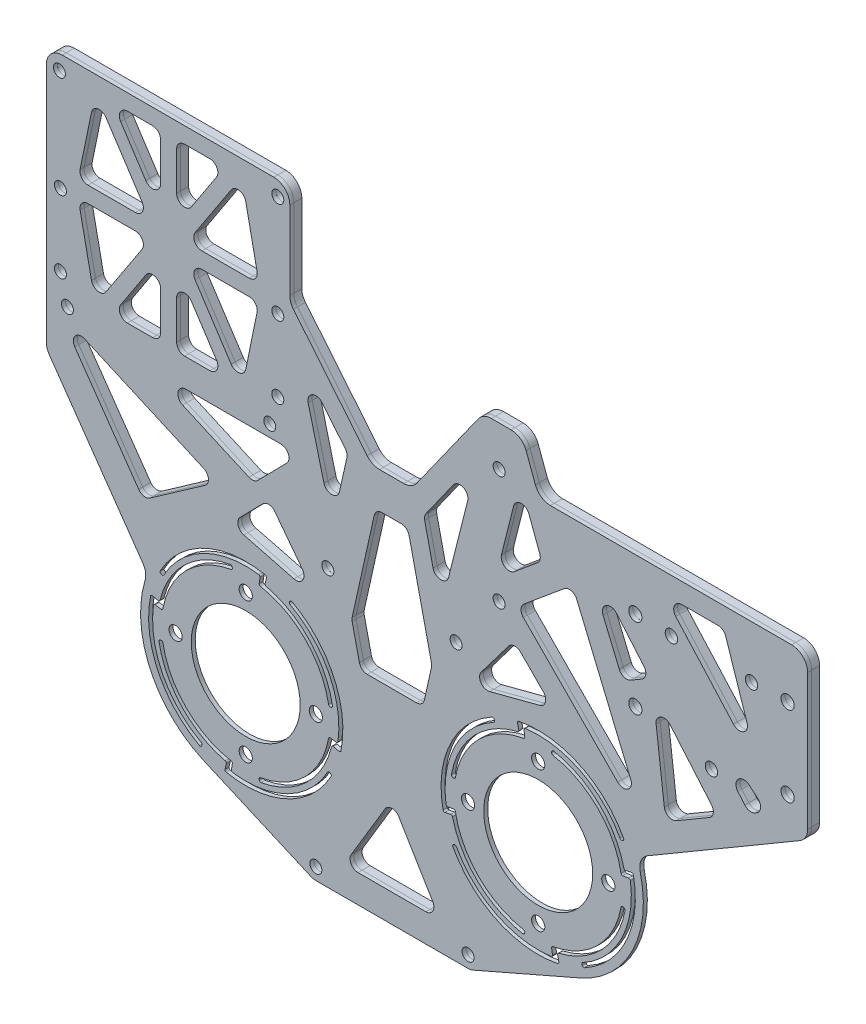
SolidWorks part; units mm, degrees
material "碳1"
ref_plane "前视基准面" through (0, 0, 0) normal (0, 0, 1) x (1, 0, 0)
ref_plane "上视基准面" through (0, 0, 0) normal (0, 1, 0) x (1, 0, 0)
ref_plane "右视基准面" through (0, 0, 0) normal (1, 0, 0) x (0, 0, -1)
sketch "草图1" plane through (0, 0, 0) normal (0, 0, 1) x (1, 0, 0)
  line L0 (-404.6498, 0) -> (19827.8382, 0) construction
  line L1 (0, -404.6498) -> (0, 19827.8382) construction
  circle A0 centre (36.5, 0) radius 17.5 construction
  circle A1 centre (-36.5, 0) radius 17.5 construction
  circle A2 centre (19, 0) radius 1.65
  circle A3 centre (36.5, 17.5) radius 1.65
  circle A4 centre (54, 0) radius 1.65
  circle A5 centre (36.5, -17.5) radius 1.65
  circle A6 centre (-19, 0) radius 1.65
  circle A7 centre (-36.5, -17.5) radius 1.65
  circle A8 centre (-54, 0) radius 1.65
  circle A9 centre (-36.5, 17.5) radius 1.65
  circle A10 centre (36.5, 0) radius 13.6
  circle A11 centre (-36.5, 0) radius 13.6
  circle A12 centre (36.5, 0) radius 21
  circle A13 centre (-36.5, 0) radius 21
  point P20 (36.5, 0)
  dimension "D1" = 73
  dimension "D2" = 35
  dimension "D3" = 3.3
  dimension "D5" = 27.2
  dimension "D6" = 42
  dimension "D4" = 4
extrude "凸台-拉伸1" add sketch "草图1" along normal blind 3
sketch "草图2" plane through (0, 0, 3) normal (0, 0, 1) x (1, 0, 0)
  line L0 (0, -1000) -> (0, 49000) construction
  line L1 (36.5, -1000) -> (36.5, 49000) construction
  line L2 (-965, 0) -> (49035, 0) construction
  line L3 (36.1795, 0.8807) -> (-17028.2448, 46885.001) construction
  line L4 (14.7709, 3.4416) -> (15.7585, 3.2851)
  line L5 (13.5362, -3.6371) -> (15.7585, -3.2851)
  line L6 (57.9785, 4.7617) -> (60.1752, 5.2487)
  line L7 (31.7383, 21.4785) -> (31.2513, 23.6752)
  line L8 (25.3026, 21.51) -> (25.7643, 20.623)
  line L9 (58.01, 11.1974) -> (57.123, 10.7357)
  line L10 (39.9416, 21.7291) -> (39.7851, 20.7415)
  line L11 (32.8629, 22.9638) -> (33.2149, 20.7415)
  line L12 (41.2617, -21.4785) -> (41.7487, -23.6752)
  line L13 (47.6974, -21.51) -> (47.2357, -20.623)
  line L14 (58.2291, -3.4416) -> (57.2415, -3.2851)
  line L15 (59.4638, 3.6371) -> (57.2415, 3.2851)
  line L16 (15.0215, -4.7617) -> (12.8248, -5.2487)
  line L17 (14.99, -11.1974) -> (15.877, -10.7357)
  line L18 (33.0584, -21.7291) -> (33.2149, -20.7415)
  line L19 (40.1371, -22.9638) -> (39.7851, -20.7415)
  line L20 (-40.1371, -22.9638) -> (-39.7851, -20.7415)
  line L21 (-33.0584, -21.7291) -> (-33.2149, -20.7415)
  line L22 (-14.99, -11.1974) -> (-15.877, -10.7357)
  line L23 (-15.0215, -4.7617) -> (-12.8248, -5.2487)
  line L24 (-59.4638, 3.6371) -> (-57.2415, 3.2851)
  line L25 (-58.2291, -3.4416) -> (-57.2415, -3.2851)
  line L26 (-47.6974, -21.51) -> (-47.2357, -20.623)
  line L27 (-41.2617, -21.4785) -> (-41.7487, -23.6752)
  line L28 (-32.8629, 22.9638) -> (-33.2149, 20.7415)
  line L29 (-39.9416, 21.7291) -> (-39.7851, 20.7415)
  line L30 (-58.01, 11.1974) -> (-57.123, 10.7357)
  line L31 (-25.3026, 21.51) -> (-25.7643, 20.623)
  line L32 (-31.7383, 21.4785) -> (-31.2513, 23.6752)
  line L33 (-57.9785, 4.7617) -> (-60.1752, 5.2487)
  line L34 (-13.5362, -3.6371) -> (-15.7585, -3.2851)
  line L35 (-14.7709, 3.4416) -> (-15.7585, 3.2851)
  arc A1 (32.8629, 22.9638) -> (57.123, 10.7357) centre (36.5, 0) cw
  arc A2 (39.9416, 21.7291) -> (57.9785, 4.7617) centre (36.5, 0) cw
  circle A3 centre (36.5, 0) radius 21 construction
  arc A4 (13.5362, -3.6371) -> (25.7643, 20.623) centre (36.5, 0) cw
  arc A5 (14.7709, 3.4416) -> (31.7383, 21.4785) centre (36.5, 0) cw
  arc A6 (25.3026, 21.51) -> (31.2513, 23.6752) centre (36.5, 0) cw
  circle A7 centre (36.5, 0) radius 24.25
  circle A8 centre (36.5, 0) radius 26.25
  arc A9 (59.4638, 3.6371) -> (47.2357, -20.623) centre (36.5, 0) cw
  arc A10 (58.2291, -3.4416) -> (41.2617, -21.4785) centre (36.5, 0) cw
  arc A11 (40.1371, -22.9638) -> (15.877, -10.7357) centre (36.5, 0) cw
  arc A12 (33.0584, -21.7291) -> (15.0215, -4.7617) centre (36.5, 0) cw
  arc A13 (-33.0584, -21.7291) -> (-15.0215, -4.7617) centre (-36.5, 0) ccw
  arc A14 (-40.1371, -22.9638) -> (-15.877, -10.7357) centre (-36.5, 0) ccw
  arc A15 (-58.2291, -3.4416) -> (-41.2617, -21.4785) centre (-36.5, 0) ccw
  arc A16 (-59.4638, 3.6371) -> (-47.2357, -20.623) centre (-36.5, 0) ccw
  circle A17 centre (-36.5, 0) radius 26.25
  circle A18 centre (-36.5, 0) radius 24.25
  arc A19 (-25.3026, 21.51) -> (-31.2513, 23.6752) centre (-36.5, 0) ccw
  arc A20 (-14.7709, 3.4416) -> (-31.7383, 21.4785) centre (-36.5, 0) ccw
  arc A21 (-13.5362, -3.6371) -> (-25.7643, 20.623) centre (-36.5, 0) ccw
  arc A22 (-39.9416, 21.7291) -> (-57.9785, 4.7617) centre (-36.5, 0) ccw
  arc A23 (-32.8629, 22.9638) -> (-57.123, 10.7357) centre (-36.5, 0) ccw
  circle A24 centre (-36.5, 0) radius 21 construction
  circle A25 centre (-36.5, 0) radius 21
  point P50 (36.5, 0)
  point P84 (-36.5, 0)
  circle M14 centre (36.5, 0) radius 21
  dimension "D1" = 18
  dimension "D2" = 20
  dimension "D3" = 1
  dimension "D4" = 4
  dimension "D5" = 1.25
  dimension "D7" = 1
  dimension "D8" = 2
  dimension "D6" = 15
extrude "凸台-拉伸2" add sketch "草图2" against normal blind 3 contours A8 A7 A6 | A6 L8 A4 L5 L4 A5 L7 M14 | L6 A7 L9 A1 L11 L10 A2 M14 | L14 A10 L12 A7 L13 A9 L15 M14 | L18 A12 L16 A7 L17 A11 L19 M14 | A25 L28 A23 L30 A18 L33 A22 L29 | A25 L34 A21 L31 A18 L32 A20 L35 | A17 A18 | A25 L20 A14 L22 A18 L23 A13 L21 | A25 L24 A16 L26 A18 L27 A15 L25 region at (15.2131, 3.0376, 3) region at (33.3646, 21.9042, 3) region at (36.5, -21.3298, 3) region at (58.4042, 3.1354, 3) region at (-39.6354, -21.9042, 3) region at (-57.7869, -3.0376, 3) region at (-15.2359, -1.6735, 3) region at (-39.5376, 21.2869, 3) region at (10.9925, 0, 3) region at (-62.0075, 0, 3)
fillet "圆角1" radius 0.4 32 edges at (39.7851, 20.7415, 1.5) (39.9416, 21.7291, 1.5) (33.2149, 20.7415, 1.5) (32.8629, 22.9638, 1.5) (25.7643, 20.623, 1.5) (47.6974, -21.51, 1.5) (25.3026, 21.51, 1.5) (31.7383, 21.4785, 1.5) (31.2513, 23.6752, 1.5) (41.7487, -23.6752, 1.5) (57.9785, 4.7617, 1.5) (60.1752, 5.2487, 1.5) (12.8248, -5.2487, 1.5) (47.2357, -20.623, 1.5) (59.4638, 3.6371, 1.5) (57.2415, 3.2851, 1.5) (57.2415, -3.2851, 1.5) (58.2291, -3.4416, 1.5) (41.2617, -21.4785, 1.5) (58.01, 11.1974, 1.5) (14.99, -11.1974, 1.5) (15.877, -10.7357, 1.5) (40.1371, -22.9638, 1.5) (39.7851, -20.7415, 1.5) (33.2149, -20.7415, 1.5) (33.0584, -21.7291, 1.5) (15.0215, -4.7617, 1.5) (13.5362, -3.6371, 1.5) (15.7585, -3.2851, 1.5) (14.7709, 3.4416, 1.5) (57.123, 10.7357, 1.5) (15.7585, 3.2851, 1.5)
fillet "圆角2" radius 0.4 32 edges at (-32.8629, 22.9638, 1.5) (-57.123, 10.7357, 1.5) (-14.99, -11.1974, 1.5) (-58.01, 11.1974, 1.5) (-31.7383, 21.4785, 1.5) (-14.7709, 3.4416, 1.5) (-15.7585, 3.2851, 1.5) (-33.2149, 20.7415, 1.5) (-15.7585, -3.2851, 1.5) (-13.5362, -3.6371, 1.5) (-25.7643, 20.623, 1.5) (-47.6974, -21.51, 1.5) (-25.3026, 21.51, 1.5) (-60.1752, 5.2487, 1.5) (-12.8248, -5.2487, 1.5) (-15.0215, -4.7617, 1.5) (-33.0584, -21.7291, 1.5) (-33.2149, -20.7415, 1.5) (-39.7851, -20.7415, 1.5) (-40.1371, -22.9638, 1.5) (-15.877, -10.7357, 1.5) (-41.7487, -23.6752, 1.5) (-31.2513, 23.6752, 1.5) (-41.2617, -21.4785, 1.5) (-58.2291, -3.4416, 1.5) (-57.2415, -3.2851, 1.5) (-57.2415, 3.2851, 1.5) (-59.4638, 3.6371, 1.5) (-47.2357, -20.623, 1.5) (-57.9785, 4.7617, 1.5) (-39.9416, 21.7291, 1.5) (-39.7851, 20.7415, 1.5)
sketch "草图3" plane through (0, 0, 3) normal (0, 0, 1) x (1, 0, 0)
  line L0 (0, -33) -> (0, 33) construction
  line L1 (-19, -33) -> (19, -33) construction
  line L2 (-16, 33) -> (16, 33) construction
  line L3 (-46.9959, -24.0603) -> (-20.1995, -35.7498)
  line L4 (-19, -36) -> (19, -36)
  line L5 (20.1995, -35.7498) -> (46.9959, -24.0603)
  line L6 (-48.5, 23.3466) -> (-48.5, 36)
  line L7 (-48.5, 36) -> (48.5, 36)
  line L8 (48.5, 36) -> (48.5, 23.3466)
  circle A0 centre (16, 33) radius 1.5
  circle A1 centre (-16, 33) radius 1.5
  circle A2 centre (-19, -33) radius 1.5
  circle A3 centre (19, -33) radius 1.5
  arc A4 (-46.9959, -24.0603) -> (-48.5, 23.3466) centre (-36.5, 0) ccw
  arc A5 (48.5, 23.3466) -> (46.9959, -24.0603) centre (36.5, 0) ccw
  arc A6 (-20.1995, -35.7498) -> (-19, -36) centre (-19, -33) ccw
  arc A7 (19, -36) -> (20.1995, -35.7498) centre (19, -33) ccw
  circle A8 centre (36.5, 0) radius 26.25 construction
  point P4 (0, 0)
  point P8 (0, -33)
  point P11 (0, 33)
  dimension "D4" = 3
  dimension "D5" = 6
  dimension "D6" = 6
  dimension "D7" = 52.5
  dimension "D8" = 52.5
  dimension "D1" = 66
  dimension "D2" = 38
  dimension "D3" = 32
  dimension "D9" = 3
  dimension "D10" = 12
  dimension "D11" = 12
extrude "凸台-拉伸3" add sketch "草图3" against normal blind 3
sketch "草图4" plane through (0, 0, 3) normal (0, 0, 1) x (1, 0, 0)
  line L0 (-48.5, 36) -> (-48.5, 85.8)
  line L1 (-48.5, 85.8) -> (48.5, 85.8)
  line L2 (48.5, 85.8) -> (48.5, 36)
  line L3 (-48.5, 36) -> (48.5, 36)
  dimension "D1" = 49.8
extrude "凸台-拉伸4" add sketch "草图4" against normal blind 3
sketch "草图5" plane through (0, 0, 3) normal (0, 0, 1) x (1, 0, 0)
  line L0 (-48.5, 85.8) -> (-48.5, 23.3466) construction
  line L3 (48.5, 85.8) -> (-48.5, 85.8) construction
  line L5 (-28.5, 63.8) -> (-28.5, 81.8) construction
  circle A1 centre (-28.5, 81.8) radius 1.5
  circle A3 centre (-28.5, 63.8) radius 1.5
  dimension "D1" = 20
  dimension "D3" = 3
  dimension "D4" = 3
  dimension "D2" = 4
  dimension "D5" = 18
extrude "切除-拉伸1" cut sketch "草图5" against normal blind 4
sketch "草图6" plane through (0, 0, 3) normal (0, 0, 1) x (1, 0, 0)
  line L0 (-47.3, 72.8) -> (-28.5, 72.8) construction
  line L1 (-37.9, 72.8) -> (-37.9, 32.5) construction
  line L2 (-28.5, 72.8) -> (-28.5, 81.8) construction
  line L3 (-48.5, 85.8) -> (-72.5, 33.96)
  line L5 (-72.5, 23.2101) -> (-72.5, 33.96)
  line L6 (0, 0) -> (0, 85.8) construction
  line L7 (48.5, 85.8) -> (-48.5, 85.8) construction
  line L8 (-48.5, 85.8) -> (-48.5, 23.3466)
  line L9 (-72.5, 23.2101) -> (-61.2605, -8.7167)
  arc A0 (-48.5, 23.3466) -> (-61.2605, -8.7167) centre (-36.5, 0) ccw
  arc A1 (-48.5, 23.3466) -> (-46.9959, -24.0603) centre (-36.5, 0) ccw construction
  dimension "D6" = 9
  dimension "D1" = 40.3
  dimension "D2" = 24.842
  dimension "D3" = 72.5
  dimension "D4" = 160.606
  dimension "D5" = 9.4
extrude "凸台-拉伸5" add sketch "草图6" against normal blind 3
sketch "草图7" plane through (0, 0, 3) normal (0, 0, 1) x (1, 0, 0)
  line L1 (48.5, 85.8) -> (-48.5, 85.8) construction
  line L2 (32.5, 85.8) -> (32.5, 25.9434) construction
  line L3 (48.5, 23.3466) -> (48.5, 85.8) construction
  line L5 (32.5, 85.8) -> (48.5, 23.3466)
  line L6 (48.5, 23.3466) -> (48.5, 85.8)
  line L7 (48.5, 85.8) -> (32.5, 85.8)
  dimension "D2" = 16
extrude "切除-拉伸2" cut sketch "草图7" against normal blind 10
sketch "草图8" plane through (0, 0, 3) normal (0, 0, 1) x (1, 0, 0)
  line L0 (32.5, 85.8) -> (61.0934, 9.1776)
  line L1 (48.5, 23.3466) -> (32.5, 85.8)
  arc A0 (46.9959, -24.0603) -> (48.5, 23.3466) centre (36.5, 0) ccw construction
  arc A1 (61.0934, 9.1776) -> (48.5, 23.3466) centre (36.5, 0) ccw
extrude "凸台-拉伸6" add sketch "草图8" against normal blind 3
sketch "草图9" plane through (0, 0, 3) normal (0, 0, 1) x (1, 0, 0)
  line L0 (32.5, 85.8) -> (-48.5, 85.8) construction
  line L1 (26.75, 75.8) -> (26.75, 47.2) construction
  circle A0 centre (26.75, 75.8) radius 1.5
  circle A1 centre (26.75, 47.2) radius 1.5
  dimension "D1" = 10
  dimension "D2" = 5.75
  dimension "D3" = 3
  dimension "D4" = 3
  dimension "D5" = 28.6
extrude "切除-拉伸3" cut sketch "草图9" against normal blind 9
sketch "草图12" plane through (0, 0, 0) normal (0, 0, -1) x (-1, 0, 0)
  line L0 (-22.75, 85.8) -> (-5, 60.8)
  line L1 (-5, 60.8) -> (5, 60.8)
  line L2 (5, 60.8) -> (25.5, 85.8)
  line L3 (-32.5, 85.8) -> (48.5, 85.8) construction
  line L4 (0, 60.8) -> (0, 0) construction
  line L5 (-22.75, 85.8) -> (25.5, 85.8)
  circle A1 centre (-26.75, 75.8) radius 1.5 construction
  circle A2 centre (28.5, 81.8) radius 1.5 construction
  dimension "D3" = 3
  dimension "D4" = 4
  dimension "D1" = 25
  dimension "D2" = 10
extrude "切除-拉伸5" cut sketch "草图12" against normal blind 10
sketch "草图16" plane through (0, 0, 0) normal (0, 0, -1) x (-1, 0, 0)
  line L0 (48.5, 85.8) -> (35.25, 85.8)
  line L1 (25.5, 85.8) -> (48.5, 85.8) construction
  line L2 (72.5, 33.96) -> (72.5, 23.2101) construction
  line L3 (48.5, 85.8) -> (72.5, 33.96) construction
  line L4 (72.5, 33.96) -> (72.5, 23.2101)
  line L5 (48.5, 85.8) -> (72.5, 33.96)
  line L7 (72.5, 23.2101) -> (61.2605, -8.7167) construction
  line L8 (72.5, 23.2101) -> (64.2654, -0.1809)
  line L9 (35.25, 85.8) -> (64.2654, -0.1809)
  circle A1 centre (36.5, 0) radius 26.25 construction
  dimension "D3" = 52.5
  dimension "D1" = 9.75
extrude "切除-拉伸9" cut sketch "草图16" against normal blind 10
sketch "草图18" plane through (0, 0, 0) normal (0, 0, -1) x (-1, 0, 0)
  line L1 (25.5, 110.8) -> (64.2654, 110.8)
  line L2 (35.25, 85.8) -> (64.2654, -0.1809) construction
  line L3 (64.2654, 110.8) -> (64.2654, -0.1809)
  line L4 (35.25, 85.8) -> (64.2654, -0.1809)
  line L5 (25.5, 85.8) -> (25.5, 110.8)
  line L6 (25.5, 85.8) -> (35.25, 85.8) construction
  line L7 (25.5, 85.8) -> (35.25, 85.8)
  dimension "D1" = 25
extrude "凸台-拉伸7" add sketch "草图18" against normal up to surface (3 mm away) up to face at (-4.3272, 17.9362, 3)
sketch "草图21" plane through (-64.2654, 0, 0) normal (-1, 0, 0) x (0, 0, 1)
  line L4 (0, -0.1809) -> (3, -0.1809)
  line L5 (3, -0.1809) -> (3, 110.8)
  line L6 (3, 110.8) -> (0, 110.8)
  line L7 (0, 110.8) -> (0, -0.1809)
  line L8 (0, -0.1809) -> (3, -0.1809)
  line L9 (3, -0.1809) -> (3, 110.8)
  line L10 (3, 110.8) -> (0, 110.8)
  line L11 (0, 110.8) -> (0, -0.1809)
  dimension "D1" = 0
extrude "凸台-拉伸8" add sketch "草图21" along normal blind 22
sketch "草图20" plane through (0, 0, 3) normal (0, 0, 1) x (1, 0, 0)
  line L0 (-81, 57) -> (-30.5, 57) construction
  line L1 (-28.5, 107.08) -> (-30.5, 107.08) construction
  line L2 (-30.5, 107.08) -> (-30.5, 57) construction
  line L3 (-55.75, 57) -> (-55.75, 110.8) construction
  line L5 (-86.2654, 110.8) -> (-25.5, 110.8) construction
  circle A0 centre (-30.5, 57) radius 1.5
  circle A1 centre (-81, 57) radius 1.5
  circle A3 centre (-28.5, 63.8) radius 1.5 construction
  circle A5 centre (-28.5, 107.08) radius 1.5
  circle A7 centre (-83, 107.08) radius 1.5
  circle A8 centre (-28.5, 63.8) radius 1.5 construction
  dimension "D1" = 6.8
  dimension "D4" = 3
  dimension "D6" = 3
  dimension "D2" = 2
  dimension "D3" = 50.5
  dimension "D5" = 50.08
  dimension "D8" = 2
extrude "切除-拉伸10" cut sketch "草图20" against normal blind 25 contours A7 | A1 | A0 | A5 region at (-30.5, 57, 3) region at (-81, 57, 3) region at (-83, 107.08, 3)
sketch "草图22" plane through (0, 0, 0) normal (0, 0, -1) x (-1, 0, 0)
  line L0 (86.2654, 110.8) -> (86.2654, -0.1809) construction
  line L1 (86.2654, 45.4415) -> (86.2654, -0.1809)
  line L2 (86.2654, -0.1809) -> (64.2654, -0.1809) construction
  line L3 (64.2654, -0.1809) -> (61.2605, -8.7167) construction
  line L4 (64.2654, -0.1809) -> (61.2605, -8.7167)
  line L5 (86.2654, -0.1809) -> (64.2654, -0.1809)
  line L6 (86.2654, 45.4415) -> (61.0162, 9.3818)
  circle A1 centre (36.5, 0) radius 26.25
  arc A2 (86.2654, 45.4415) -> (47.4807, 23.843) centre (86.2654, -0.1809) ccw
  dimension "D1" = 52.5
  dimension "D2" = 45.6223
  dimension "D3" = 35
extrude "切除-拉伸11" cut sketch "草图22" against normal blind 45.6223 contours A1 L4 L5 L1 L6 region at (-76.5446, 15.6627, 0)
sketch "草图27" plane through (0, 0, 0) normal (0, 0, -1) x (-1, 0, 0)
  line L0 (-61.0934, 9.1776) -> (-32.5, 85.8) construction
  line L1 (-61.0934, 9.1776) -> (-32.5, 85.8)
  line L2 (-61.0934, 9.1776) -> (-61.0934, 85.8)
  line L3 (-61.0934, 85.8) -> (-32.5, 85.8)
  line L4 (-61.0934, 74.35) -> (-36.7728, 74.35)
  dimension "D1" = 11.45
extrude "凸台-拉伸10" add sketch "草图27" against normal up to surface (3 mm away) contours L4 L2 L1 region at (52.9865, 52.6259, 0) up to face at (-81.5, 107.08, 3)
sketch "草图28" plane through (61.0934, 0, 0) normal (1, 0, 0) x (0, 0, -1)
  line L4 (-3, 74.35) -> (-3, 9.1776)
  line L5 (-3, 9.1776) -> (0, 9.1776)
  line L6 (0, 9.1776) -> (0, 74.35)
  line L7 (0, 74.35) -> (-3, 74.35)
  line L8 (-3, 74.35) -> (-3, 9.1776)
  line L9 (-3, 9.1776) -> (0, 9.1776)
  line L10 (0, 9.1776) -> (0, 74.35)
  line L11 (0, 74.35) -> (-3, 74.35)
  dimension "D1" = 0
extrude "凸台-拉伸11" add sketch "草图28" along normal blind 42.66
sketch "草图29" plane through (0, 0, 3) normal (0, 0, 1) x (1, 0, 0)
  line L0 (61.0934, 9.1776) -> (103.7534, 34.1776)
  line L1 (103.7534, 74.35) -> (103.7534, 9.1776) construction
  line L2 (103.7534, 34.1776) -> (103.7534, 9.1776)
  line L3 (103.7534, 9.1776) -> (61.0934, 9.1776) construction
  line L4 (103.7534, 9.1776) -> (61.0934, 9.1776)
  dimension "D1" = 25
extrude "切除-拉伸15" cut sketch "草图29" against normal blind 30
fillet "圆角5" radius 4 9 edges at (22.75, 85.8, 1.5) (32.5, 85.8, 1.5) (-5, 60.8, 1.5) (5, 60.8, 1.5) (-25.5, 85.8, 1.5) (-25.5, 110.8, 1.5) (-86.2654, 110.8, 1.5) (-61.0162, 9.3818, 1.5) (-86.2654, 45.4415, 1.5)
sketch "草图13" plane through (0, 0, 0) normal (0, 0, -1) x (-1, 0, 0)
  line L5 (-12, -29) -> (12, -29)
  line L6 (12, -29) -> (0, -9)
  line L7 (0, -9) -> (0, 0) construction
  line L8 (0, -9) -> (-12, -29)
  line L9 (19, -36) -> (-19, -36) construction
  line L10 (0, -29) -> (0, -36) construction
  dimension "D1" = 7
  dimension "D2" = 9
  dimension "D3" = 24
extrude "切除-拉伸6" cut sketch "草图13" against normal blind 10
fillet "圆角7" radius 2 3 edges at (-12, -29, 1.5) (12, -29, 1.5) (0, -9, 1.5)
sketch "草图14" plane through (0, 0, 0) normal (0, 0, -1) x (-1, 0, 0)
  line L3 (28.5, 81.8) -> (16, 33) construction
  line L4 (11.0339, 60.273) -> (23.1612, 75.0623)
  line L5 (23.1612, 75.0623) -> (14.9105, 42.8516)
  line L6 (14.9105, 42.8516) -> (11.0339, 60.273)
  line L7 (-26.75, 75.8) -> (-16, 33) construction
  line L8 (6.2002, 62.2637) -> (24.5931, 84.694) construction
  line L9 (11.0339, 60.273) -> (22.25, 57.4) construction
  line L10 (-21.4921, 75.3916) -> (-12.1005, 38)
  line L11 (-12.1005, 38) -> (-7.967, 56.3421)
  line L12 (-7.967, 56.3421) -> (-21.4921, 75.3916)
  line L13 (-21.5541, 84.1157) -> (-6.1959, 62.4843) construction
  line L14 (-2.9343, 60.8) -> (3.1071, 60.8) construction
  line L18 (18.8616, 25.035) -> (30.6177, 40.4726)
  line L19 (28.5, 63.8) -> (28.5, 43.5843) construction
  line L20 (40.3313, 30.591) -> (18.8616, 25.035)
  line L21 (30.6177, 40.4726) -> (40.3313, 30.591)
  line L26 (0.0864, 60.8) -> (0, 0) construction
  line L27 (-3.9264, 51.8) -> (4.0736, 51.8)
  line L28 (4.0736, 51.8) -> (10.0371, 25)
  line L29 (10.0371, 25) -> (7.7835, 15)
  line L30 (7.7835, 15) -> (-7.7408, 15)
  line L31 (-7.7408, 15) -> (-9.966, 25)
  line L32 (-9.966, 25) -> (-3.9264, 51.8)
  line L33 (-9.966, 25) -> (10.0371, 25) construction
  line L34 (-30.5025, 40.5595) -> (-40.2442, 30.7055)
  line L35 (-40.2442, 30.7055) -> (-18.7904, 25.0885)
  line L36 (-18.7904, 25.0885) -> (-30.5025, 40.5595)
  line L37 (-26.75, 47.2) -> (-16, 33) construction
  line L38 (-26.75, 47.2) -> (-65.6286, 7.8733) construction
  line L45 (16, 33) -> (28.5, 43.5843) construction
  arc A1 (-61.0934, 9.1776) -> (-46.9959, -24.0603) centre (-36.5, 0) ccw construction
  circle A4 centre (28.5, 63.8) radius 1.5 construction
  circle A5 centre (28.5, 63.8) radius 1.5
  point P22 (0.0213, 15)
  dimension "D1" = 7
  dimension "D2" = 5
  dimension "D3" = 35.377
  dimension "D4" = 102.7
  dimension "D5" = 5
  dimension "D6" = 10
  dimension "D7" = 5
  dimension "D12" = 9
  dimension "D13" = 8
  dimension "D14" = 4
  dimension "D15" = 15
  dimension "D16" = 10
  dimension "D17" = 7
  dimension "D18" = 4
  dimension "D19" = 60
  dimension "D20" = 12
extrude "切除-拉伸7" cut sketch "草图14" against normal blind 10
fillet "圆角8" radius 2 18 edges at (-23.1612, 75.0623, 1.5) (-14.9105, 42.8516, 1.5) (18.7904, 25.0885, 1.5) (40.2442, 30.7055, 1.5) (30.5025, 40.5595, 1.5) (3.9264, 51.8, 1.5) (-4.0736, 51.8, 1.5) (-10.0371, 25, 1.5) (-7.7835, 15, 1.5) (7.7408, 15, 1.5) (9.966, 25, 1.5) (-11.0339, 60.273, 1.5) (7.967, 56.3421, 1.5) (12.1005, 38, 1.5) (21.4921, 75.3916, 1.5) (-30.6177, 40.4726, 1.5) (-40.3313, 30.591, 1.5) (-18.8616, 25.035, 1.5)
sketch "草图23" plane through (0, 0, 0) normal (0, 0, -1) x (-1, 0, 0)
  line L0 (30.5, 57) -> (81, 57) construction
  line L1 (78.3326, 85.9) -> (60.3326, 85.9)
  line L2 (55.75, 57) -> (55.75, 110.8) construction
  line L3 (82.2654, 110.8) -> (29.5, 110.8) construction
  line L4 (41.75, 106.8) -> (53.75, 106.8)
  line L5 (53.75, 106.8) -> (53.75, 88.4826)
  line L6 (53.75, 88.4826) -> (41.75, 106.8)
  line L7 (55.75, 83.9) -> (86.2654, 83.9) construction
  line L8 (86.2654, 106.8) -> (86.2654, 46.7027) construction
  line L9 (55.75, 83.9) -> (30.5, 83.9) construction
  line L10 (51.1674, 85.9) -> (37.4755, 106.8)
  line L11 (37.4755, 106.8) -> (33.1674, 85.9)
  line L12 (33.1674, 85.9) -> (51.1674, 85.9)
  line L13 (74.0245, 106.8) -> (78.3326, 85.9)
  line L14 (60.3326, 85.9) -> (74.0245, 106.8)
  line L15 (57.75, 88.4826) -> (69.75, 106.8)
  line L16 (57.75, 106.8) -> (57.75, 88.4826)
  line L17 (69.75, 106.8) -> (57.75, 106.8)
  line L18 (69.75, 61) -> (57.75, 61)
  line L19 (57.75, 61) -> (57.75, 79.3174)
  line L20 (57.75, 79.3174) -> (69.75, 61)
  line L21 (60.3326, 81.9) -> (74.0245, 61)
  line L22 (74.0245, 61) -> (78.3326, 81.9)
  line L23 (33.1674, 81.9) -> (51.1674, 81.9)
  line L24 (37.4755, 61) -> (33.1674, 81.9)
  line L25 (51.1674, 81.9) -> (37.4755, 61)
  line L26 (53.75, 79.3174) -> (41.75, 61)
  line L27 (53.75, 61) -> (53.75, 79.3174)
  line L28 (41.75, 61) -> (53.75, 61)
  line L29 (78.3326, 81.9) -> (60.3326, 81.9)
  line L30 (22.9292, 54) -> (34.439, 42.2911)
  line L31 (34.439, 42.2911) -> (60.9292, 54)
  line L32 (60.9292, 54) -> (22.9292, 54)
  line L33 (37.9029, 33.0614) -> (32.2363, 38.826) construction
  line L34 (43.7425, 37.6567) -> (62.065, 24.8272)
  line L35 (62.065, 24.8272) -> (83.2873, 55.1358)
  line L36 (83.2873, 55.1358) -> (43.7425, 37.6567)
  line L39 (85.542, 44.4084) -> (62.1803, 11.0443) construction
  circle A1 centre (55.75, 83.9) radius 5
  dimension "D1" = 10
  dimension "D2" = 4
  dimension "D3" = 2
  dimension "D4" = 4
  dimension "D5" = 12
  dimension "D6" = 18
  dimension "D7" = 3
  dimension "D8" = 4
  dimension "D9" = 110.663
  dimension "D10" = 38
  dimension "D11" = 8
  dimension "D12" = 90
  dimension "D13" = 37
  dimension "D14" = 8
extrude "切除-拉伸12" cut sketch "草图23" against normal blind 110.663 contours L11 L12 L10 | L6 L5 L4 | L15 L17 L16 | L14 L1 L13 | L22 L29 L21 | L20 L19 L18 | L26 L28 L27 | L25 L23 L24 | L35 L36 L34 | L32 L30 L31 | L36 L34 L35 region at (-70.8965, 74.9333, 0) region at (-61.75, 67.1058, 0) region at (-49.75, 67.1058, 0) region at (-40.6035, 74.9333, 0) region at (-40.6035, 92.8667, 0) region at (-49.75, 100.6942, 0) region at (-61.75, 100.6942, 0) region at (-70.8965, 92.8667, 0) region at (-63.0316, 39.2066, 0)
fillet "圆角9" radius 2 30 edges at (-57.75, 61, 1.5) (-69.75, 61, 1.5) (-57.75, 79.3174, 1.5) (-53.75, 61, 1.5) (-41.75, 61, 1.5) (-53.75, 79.3174, 1.5) (-33.1674, 81.9, 1.5) (-37.4755, 61, 1.5) (-51.1674, 81.9, 1.5) (-74.0245, 61, 1.5) (-78.3326, 81.9, 1.5) (-60.3326, 81.9, 1.5) (-78.3326, 85.9, 1.5) (-74.0245, 106.8, 1.5) (-60.3326, 85.9, 1.5) (-57.75, 88.4826, 1.5) (-69.75, 106.8, 1.5) (-57.75, 106.8, 1.5) (-53.75, 106.8, 1.5) (-53.75, 88.4826, 1.5) (-41.75, 106.8, 1.5) (-51.1674, 85.9, 1.5) (-33.1674, 85.9, 1.5) (-37.4755, 106.8, 1.5) (-34.439, 42.2911, 1.5) (-60.9292, 54, 1.5) (-22.9292, 54, 1.5) (-83.2873, 55.1358, 1.5) (-62.065, 24.8272, 1.5) (-43.7425, 37.6567, 1.5)
sketch "草图31" plane through (0, 0, 3) normal (0, 0, 1) x (1, 0, 0)
  line L0 (103.7534, 74.35) -> (36.7728, 74.35) construction
  line L1 (103.7534, 24.35) -> (55.7534, 24.35) construction
  line L2 (103.7534, 24.35) -> (103.7534, 74.35) construction
  line L3 (103.7534, 74.35) -> (55.7534, 74.35) construction
  line L4 (55.7534, 24.35) -> (55.7534, 74.35) construction
  line L5 (103.7534, 24.35) -> (55.7534, 74.35) construction
  line L6 (103.7534, 74.35) -> (55.7534, 24.35) construction
  line L7 (103.7534, 74.35) -> (103.7534, 34.1776) construction
  line L8 (79.7534, 49.35) -> (79.7534, 61.225) construction
  line L9 (69.7534, 61.225) -> (89.7534, 61.225) construction
  line L10 (79.7534, 49.35) -> (79.7534, 37.475) construction
  line L11 (98.7534, 61.5) -> (98.7534, 41.5) construction
  circle A0 centre (69.7534, 61.225) radius 1.55
  circle A1 centre (89.7534, 61.225) radius 1.55
  circle A2 centre (79.7534, 37.475) radius 1.55
  circle A3 centre (98.7534, 61.5) radius 1.65
  circle A4 centre (98.7534, 41.5) radius 1.65
  circle A5 centre (60.7534, 41.5) radius 1.65
  circle A6 centre (60.7534, 61.5) radius 1.65
  point P0 (79.7534, 49.35)
  dimension "D5" = 3.1
  dimension "D6" = 3.1
  dimension "D8" = 3.1
  dimension "D12" = 3.3
  dimension "D13" = 3.3
  dimension "D1" = 48
  dimension "D2" = 50
  dimension "D3" = 11.875
  dimension "D4" = 20
  dimension "D7" = 11.875
  dimension "D9" = 12.85
  dimension "D10" = 20
  dimension "D11" = 5
extrude "切除-拉伸17" cut sketch "草图31" against normal blind 10
sketch "草图24" plane through (0, 0, 0) normal (0, 0, -1) x (-1, 0, 0)
  line L0 (82.2654, 110.8) -> (29.5, 110.8) construction
  line L1 (82.75, 81.8) -> (82.75, 63.8) construction
  line L3 (53.75, 99.9926) -> (57.75, 99.9926) construction
  line L5 (53.75, 104.8) -> (53.75, 95.1852) construction
  line L6 (57.75, 104.8) -> (57.75, 95.1852) construction
  line L7 (55.75, 99.9926) -> (55.75, 110.8) construction
  line L9 (28.5, 81.8) -> (82.75, 81.8) construction
  circle A0 centre (82.75, 81.8) radius 1.5
  circle A1 centre (82.75, 63.8) radius 1.5
  dimension "D4" = 3
  dimension "D5" = 3
  dimension "D2" = 18
  dimension "D3" = 27
extrude "切除-拉伸13" cut sketch "草图24" against normal blind 10
sketch "草图32" plane through (0, 0, 3) normal (0, 0, 1) x (1, 0, 0)
  line L14 (67.8424, 69.35) -> (82.8424, 69.35)
  line L15 (82.8424, 69.35) -> (91.6618, 42.7752)
  line L16 (31.9282, 75.8913) -> (25.8382, 51.6444)
  line L17 (25.8382, 51.6444) -> (37.3907, 61.2533)
  line L18 (37.3907, 61.2533) -> (31.9282, 75.8913)
  line L19 (14.1457, 46.1425) -> (18.8982, 65.0643) construction
  line L20 (36.7728, 74.35) -> (33.4708, 83.1985) construction
  line L21 (45.0866, 59.8502) -> (31.2479, 48.3398)
  line L22 (31.2479, 48.3398) -> (63.5879, 15.6271)
  line L23 (63.5879, 15.6271) -> (45.0866, 59.8502)
  line L24 (37.8088, 33.169) -> (32.1258, 38.9175) construction
  line L25 (57.613, 45.455) -> (64.4337, 49.4521)
  line L28 (47.7129, 69.1188) -> (57.613, 45.455)
  line L29 (103.7534, 34.1776) -> (61.0934, 9.1776) construction
  line L36 (47.7129, 69.1188) -> (64.4337, 49.4521)
  line L37 (91.6618, 42.7752) -> (67.8424, 69.35)
  line L38 (103.7534, 74.35) -> (36.7728, 74.35) construction
  line L39 (71.027, 53.9141) -> (89.1638, 32.582)
  line L40 (89.1638, 32.582) -> (93.4776, 35.11)
  line L41 (93.4776, 35.11) -> (71.027, 53.9141)
  line L42 (103.7534, 34.1776) -> (61.0934, 9.1776) construction
  line L43 (65.1318, 46.9535) -> (68.3376, 20.3773)
  line L45 (68.3376, 20.3773) -> (81.2791, 27.9614)
  line L46 (81.2791, 27.9614) -> (65.1318, 46.9535)
  circle A0 centre (26.75, 47.2) radius 1.5 construction
  circle A3 centre (89.7534, 61.225) radius 1.55 construction
  circle A4 centre (69.7534, 61.225) radius 1.55 construction
  circle A5 centre (79.7534, 37.475) radius 1.55 construction
  circle A8 centre (60.7534, 61.5) radius 1.65 construction
  circle A10 centre (60.7534, 41.5) radius 1.65 construction
  dimension "D15" = 28
  dimension "D16" = 4
  dimension "D24" = 5
  dimension "D25" = 15
  dimension "D1" = 10
  dimension "D2" = 25
  dimension "D3" = 4
  dimension "D4" = 4
  dimension "D5" = 6
  dimension "D6" = 6
  dimension "D7" = 46
  dimension "D8" = 18
  dimension "D9" = 5
  dimension "D10" = 5
  dimension "D11" = 80
  dimension "D12" = 6
  dimension "D13" = 5
  dimension "D14" = 4
  dimension "D17" = 15
  dimension "D18" = 6
  dimension "D19" = 28
  dimension "D20" = 4
  dimension "D21" = 5
  dimension "D22" = 6
  dimension "D23" = 5
extrude "切除-拉伸18" cut sketch "草图32" against normal blind 10
fillet "圆角13" radius 2 18 edges at (57.613, 45.455, 1.5) (31.2479, 48.3398, 1.5) (63.5879, 15.6271, 1.5) (45.0866, 59.8502, 1.5) (25.8382, 51.6444, 1.5) (37.3907, 61.2533, 1.5) (31.9282, 75.8913, 1.5) (64.4337, 49.4521, 1.5) (47.7129, 69.1188, 1.5) (91.6618, 42.7752, 1.5) (82.8424, 69.35, 1.5) (67.8424, 69.35, 1.5) (71.027, 53.9141, 1.5) (93.4776, 35.11, 1.5) (89.1638, 32.582, 1.5) (68.3376, 20.3773, 1.5) (81.2791, 27.9614, 1.5) (65.1318, 46.9535, 1.5)
sketch "草图25" plane through (0, 0, 3) normal (0, 0, 1) x (1, 0, 0)
  line L12 (-25.5, 87.2303) -> (-25.5, 106.8)
  line L13 (-29.5, 110.8) -> (-82.2654, 110.8)
  line L14 (-86.2654, 106.8) -> (-86.2654, 46.7027)
  line L15 (-85.542, 44.4084) -> (-62.1803, 11.0443)
  line L16 (-46.9959, -24.0603) -> (-20.1995, -35.7498)
  line L17 (-19, -36) -> (19, -36)
  line L18 (20.1995, -35.7498) -> (46.9959, -24.0603)
  line L19 (36.7728, 74.35) -> (33.4708, 83.1985)
  line L20 (29.7232, 85.8) -> (24.8157, 85.8)
  line L21 (21.5541, 84.1157) -> (6.1959, 62.4843)
  line L22 (2.9343, 60.8) -> (-3.1071, 60.8)
  line L23 (-6.2002, 62.2637) -> (-24.5931, 84.694)
  line L24 (-25.5, 87.2303) -> (-25.5, 106.8)
  line L25 (-29.5, 110.8) -> (-82.2654, 110.8)
  line L26 (-86.2654, 106.8) -> (-86.2654, 46.7027)
  line L27 (-85.542, 44.4084) -> (-62.1803, 11.0443)
  line L28 (-46.9959, -24.0603) -> (-20.1995, -35.7498)
  line L29 (-19, -36) -> (19, -36)
  line L30 (20.1995, -35.7498) -> (46.9959, -24.0603)
  line L31 (36.7728, 74.35) -> (33.4708, 83.1985)
  line L32 (29.7232, 85.8) -> (24.8157, 85.8)
  line L33 (21.5541, 84.1157) -> (6.1959, 62.4843)
  line L34 (2.9343, 60.8) -> (-3.1071, 60.8)
  line L35 (-6.2002, 62.2637) -> (-24.5931, 84.694)
  line L39 (61.0934, 9.1776) -> (103.7534, 34.1776)
  line L40 (61.0934, 9.1776) -> (103.7534, 34.1776)
  line L41 (103.7534, 34.1776) -> (103.7534, 74.35)
  line L42 (103.7534, 34.1776) -> (103.7534, 74.35)
  line L43 (103.7534, 74.35) -> (36.7728, 74.35)
  line L44 (103.7534, 74.35) -> (36.7728, 74.35)
  arc A13 (-25.5, 106.8) -> (-29.5, 110.8) centre (-29.5, 106.8) ccw
  arc A14 (-82.2654, 110.8) -> (-86.2654, 106.8) centre (-82.2654, 106.8) ccw
  arc A15 (-86.2654, 46.7027) -> (-85.542, 44.4084) centre (-82.2654, 46.7027) ccw
  arc A16 (-61.6279, 7.593) -> (-62.1803, 11.0443) centre (-65.4569, 8.75) ccw
  arc A17 (-61.6279, 7.593) -> (-46.9959, -24.0603) centre (-36.5, 0) ccw
  arc A18 (-20.1995, -35.7498) -> (-19, -36) centre (-19, -33) ccw
  arc A19 (19, -36) -> (20.1995, -35.7498) centre (19, -33) ccw
  arc A20 (46.9959, -24.0603) -> (61.0934, 9.1776) centre (36.5, 0) ccw
  arc A21 (33.4708, 83.1985) -> (29.7232, 85.8) centre (29.7232, 81.8) ccw
  arc A22 (24.8157, 85.8) -> (21.5541, 84.1157) centre (24.8157, 81.8) ccw
  arc A23 (2.9343, 60.8) -> (6.1959, 62.4843) centre (2.9343, 64.8) ccw
  arc A24 (-6.2002, 62.2637) -> (-3.1071, 60.8) centre (-3.1071, 64.8) ccw
  arc A25 (-25.5, 87.2303) -> (-24.5931, 84.694) centre (-21.5, 87.2303) ccw
  arc A26 (-25.5, 106.8) -> (-29.5, 110.8) centre (-29.5, 106.8) ccw
  arc A27 (-82.2654, 110.8) -> (-86.2654, 106.8) centre (-82.2654, 106.8) ccw
  arc A28 (-86.2654, 46.7027) -> (-85.542, 44.4084) centre (-82.2654, 46.7027) ccw
  arc A29 (-61.6279, 7.593) -> (-62.1803, 11.0443) centre (-65.4569, 8.75) ccw
  arc A30 (-61.6279, 7.593) -> (-46.9959, -24.0603) centre (-36.5, 0) ccw
  arc A31 (-20.1995, -35.7498) -> (-19, -36) centre (-19, -33) ccw
  arc A32 (19, -36) -> (20.1995, -35.7498) centre (19, -33) ccw
  arc A33 (46.9959, -24.0603) -> (61.0934, 9.1776) centre (36.5, 0) ccw
  arc A34 (33.4708, 83.1985) -> (29.7232, 85.8) centre (29.7232, 81.8) ccw
  arc A35 (24.8157, 85.8) -> (21.5541, 84.1157) centre (24.8157, 81.8) ccw
  arc A36 (2.9343, 60.8) -> (6.1959, 62.4843) centre (2.9343, 64.8) ccw
  arc A37 (-6.2002, 62.2637) -> (-3.1071, 60.8) centre (-3.1071, 64.8) ccw
  arc A38 (-25.5, 87.2303) -> (-24.5931, 84.694) centre (-21.5, 87.2303) ccw
  dimension "D1" = 0
extrude "切除-拉伸14" cut sketch "草图25" against normal blind 2
sketch "草图26" plane through (0, 0, 0) normal (0, 0, 1) x (1, 0, 0)
  line L0 (-26.2734, 50.598) -> (-33.4694, 43.2776) construction
  line L1 (-35.7042, 42.8503) -> (-52.2659, 50.1707) construction
  line L2 (-51.4573, 54) -> (-27.6997, 54) construction
  line L3 (-26.2734, 50.598) -> (-33.4694, 43.2776)
  line L4 (-35.7042, 42.8503) -> (-52.2659, 50.1707)
  line L5 (-51.4573, 54) -> (-27.6997, 54)
  line L6 (-11.2453, 59.323) -> (-13.0949, 51.0108) construction
  line L7 (-17.4372, 68.0819) -> (-11.651, 61.0255) construction
  line L8 (-16.9846, 50.949) -> (-20.9212, 66.3174) construction
  line L9 (-11.2453, 59.323) -> (-13.0949, 51.0108)
  line L10 (-17.4372, 68.0819) -> (-11.651, 61.0255)
  line L11 (-16.9846, 50.949) -> (-20.9212, 66.3174)
  line L12 (-25.5, 87.2303) -> (-25.5, 106.8)
  line L13 (-29.5, 110.8) -> (-82.2654, 110.8)
  line L14 (-86.2654, 106.8) -> (-86.2654, 46.7027)
  line L15 (-85.542, 44.4084) -> (-62.1803, 11.0443)
  line L16 (-46.9959, -24.0603) -> (-20.1995, -35.7498)
  line L17 (-19, -36) -> (19, -36)
  line L18 (20.1995, -35.7498) -> (46.9959, -24.0603)
  line L19 (36.7728, 74.35) -> (33.4708, 83.1985)
  line L20 (29.7232, 85.8) -> (24.8157, 85.8)
  line L21 (21.5541, 84.1157) -> (6.1959, 62.4843)
  line L22 (2.9343, 60.8) -> (-3.1071, 60.8)
  line L23 (-6.2002, 62.2637) -> (-24.5931, 84.694)
  line L24 (-25.5, 87.2303) -> (-25.5, 106.8)
  line L25 (-29.5, 110.8) -> (-82.2654, 110.8)
  line L26 (-86.2654, 106.8) -> (-86.2654, 46.7027)
  line L27 (-85.542, 44.4084) -> (-62.1803, 11.0443)
  line L28 (-46.9959, -24.0603) -> (-20.1995, -35.7498)
  line L29 (-19, -36) -> (19, -36)
  line L30 (20.1995, -35.7498) -> (46.9959, -24.0603)
  line L31 (36.7728, 74.35) -> (33.4708, 83.1985)
  line L32 (29.7232, 85.8) -> (24.8157, 85.8)
  line L33 (21.5541, 84.1157) -> (6.1959, 62.4843)
  line L34 (2.9343, 60.8) -> (-3.1071, 60.8)
  line L35 (-6.2002, 62.2637) -> (-24.5931, 84.694)
  line L36 (-46.6473, 35.6227) -> (-60.4267, 25.9743) construction
  line L37 (-63.2121, 26.4655) -> (-79.1723, 49.259) construction
  line L38 (-76.7254, 52.2354) -> (-46.9859, 39.0903) construction
  line L39 (-46.6473, 35.6227) -> (-60.4267, 25.9743)
  line L40 (-63.2121, 26.4655) -> (-79.1723, 49.259)
  line L41 (-76.7254, 52.2354) -> (-46.9859, 39.0903)
  line L42 (30.5497, 55.5633) -> (36.2998, 60.3459) construction
  line L43 (34.1758, 69.8685) -> (36.8946, 62.5828) construction
  line L44 (-29.2188, 38.6357) -> (-22.3607, 29.6299) construction
  line L45 (-29.2188, 38.6357) -> (-22.3607, 29.6299)
  line L46 (-24.4529, 26.482) -> (-36.9777, 29.7232) construction
  line L47 (-37.9029, 33.0614) -> (-32.2363, 38.826) construction
  line L48 (-24.4529, 26.482) -> (-36.9777, 29.7232)
  line L49 (-37.9029, 33.0614) -> (-32.2363, 38.826)
  line L50 (-57.75, 63) -> (-57.75, 72.6148) construction
  line L51 (-66.0488, 61) -> (-59.75, 61) construction
  line L52 (-61.423, 73.7108) -> (-67.7218, 64.096) construction
  line L53 (-57.75, 104.8) -> (-57.75, 95.1852) construction
  line L54 (-66.0488, 106.8) -> (-59.75, 106.8) construction
  line L55 (-61.423, 94.0892) -> (-67.7218, 103.704) construction
  line L56 (-62.3608, 78.804) -> (-71.3704, 65.0512) construction
  line L57 (-75.0022, 65.7434) -> (-77.8371, 79.4962) construction
  line L58 (-75.8783, 81.9) -> (-64.0338, 81.9) construction
  line L59 (-75.8783, 85.9) -> (-64.0338, 85.9) construction
  line L60 (-62.3608, 88.996) -> (-71.3704, 102.7488) construction
  line L61 (-75.0022, 102.0566) -> (-77.8371, 88.3038) construction
  line L62 (-57.75, 63) -> (-57.75, 72.6148)
  line L63 (-66.0488, 61) -> (-59.75, 61)
  line L64 (-61.423, 73.7108) -> (-67.7218, 64.096)
  line L65 (-57.75, 104.8) -> (-57.75, 95.1852)
  line L66 (-66.0488, 106.8) -> (-59.75, 106.8)
  line L67 (-61.423, 94.0892) -> (-67.7218, 103.704)
  line L68 (-62.3608, 78.804) -> (-71.3704, 65.0512)
  line L69 (-75.0022, 65.7434) -> (-77.8371, 79.4962)
  line L70 (-75.8783, 81.9) -> (-64.0338, 81.9)
  line L71 (-75.8783, 85.9) -> (-64.0338, 85.9)
  line L72 (-62.3608, 88.996) -> (-71.3704, 102.7488)
  line L73 (-75.0022, 102.0566) -> (-77.8371, 88.3038)
  line L74 (-35.6217, 85.9) -> (-47.4662, 85.9) construction
  line L75 (-36.4978, 102.0566) -> (-33.6629, 88.3038) construction
  line L76 (-49.1392, 88.996) -> (-40.1296, 102.7488) construction
  line L77 (-36.4978, 65.7434) -> (-33.6629, 79.4962) construction
  line L78 (-35.6217, 81.9) -> (-47.4662, 81.9) construction
  line L79 (-49.1392, 78.804) -> (-40.1296, 65.0512) construction
  line L80 (-50.077, 73.7108) -> (-43.7782, 64.096) construction
  line L81 (-45.4512, 61) -> (-51.75, 61) construction
  line L82 (-53.75, 63) -> (-53.75, 72.6148) construction
  line L83 (-35.6217, 85.9) -> (-47.4662, 85.9)
  line L84 (-36.4978, 102.0566) -> (-33.6629, 88.3038)
  line L85 (-49.1392, 88.996) -> (-40.1296, 102.7488)
  line L86 (-36.4978, 65.7434) -> (-33.6629, 79.4962)
  line L87 (-35.6217, 81.9) -> (-47.4662, 81.9)
  line L88 (-49.1392, 78.804) -> (-40.1296, 65.0512)
  line L89 (-50.077, 73.7108) -> (-43.7782, 64.096)
  line L90 (-45.4512, 61) -> (-51.75, 61)
  line L91 (-53.75, 63) -> (-53.75, 72.6148)
  line L92 (-45.4512, 106.8) -> (-51.75, 106.8) construction
  line L93 (-50.077, 94.0892) -> (-43.7782, 103.704) construction
  line L94 (-53.75, 104.8) -> (-53.75, 95.1852) construction
  line L95 (-53.75, 104.8) -> (-53.75, 95.1852)
  line L96 (-50.077, 94.0892) -> (-43.7782, 103.704)
  line L97 (-45.4512, 106.8) -> (-51.75, 106.8)
  line L98 (36.893, 29.8282) -> (24.3775, 26.5514) construction
  line L99 (22.2764, 29.6933) -> (29.1089, 38.7186) construction
  line L100 (32.1258, 38.9175) -> (37.8088, 33.169) construction
  line L101 (36.893, 29.8282) -> (24.3775, 26.5514)
  line L102 (22.2764, 29.6933) -> (29.1089, 38.7186)
  line L103 (32.1258, 38.9175) -> (37.8088, 33.169)
  line L104 (18.8982, 65.0643) -> (14.1457, 46.1425) construction
  line L105 (10.2548, 46.19) -> (8.1631, 55.4719) construction
  line L106 (-8.1351, 16.5603) -> (-9.9386, 24.5631) construction
  line L107 (6.137, 15) -> (-6.184, 15) construction
  line L108 (9.8687, 24.5628) -> (8.0892, 16.5656) construction
  line L109 (4.278, 50.2397) -> (9.8676, 25.4369) construction
  line L110 (-9.9398, 25.4372) -> (-4.422, 50.2344) construction
  line L111 (-2.4697, 51.8) -> (2.3269, 51.8) construction
  line L112 (8.4834, 57.0694) -> (15.3277, 66.7093) construction
  line L113 (18.8982, 65.0643) -> (14.1457, 46.1425)
  line L114 (10.2548, 46.19) -> (8.1631, 55.4719)
  line L115 (-8.1351, 16.5603) -> (-9.9386, 24.5631)
  line L116 (6.137, 15) -> (-6.184, 15)
  line L117 (9.8687, 24.5628) -> (8.0892, 16.5656)
  line L118 (4.278, 50.2397) -> (9.8676, 25.4369)
  line L119 (-9.9398, 25.4372) -> (-4.422, 50.2344)
  line L120 (-2.4697, 51.8) -> (2.3269, 51.8)
  line L121 (8.4834, 57.0694) -> (15.3277, 66.7093)
  line L122 (1.715, -11.8583) -> (10.1826, -25.971) construction
  line L123 (8.4676, -29) -> (-8.4676, -29) construction
  line L124 (-10.1826, -25.971) -> (-1.715, -11.8583) construction
  line L125 (1.715, -11.8583) -> (10.1826, -25.971)
  line L126 (8.4676, -29) -> (-8.4676, -29)
  line L127 (-10.1826, -25.971) -> (-1.715, -11.8583)
  line L128 (27.3311, 57.5881) -> (30.3622, 69.6564) construction
  line L129 (30.5497, 55.5633) -> (36.2998, 60.3459)
  line L130 (34.1758, 69.8685) -> (36.8946, 62.5828)
  line L131 (27.3311, 57.5881) -> (30.3622, 69.6564)
  line L136 (56.0481, 59.3152) -> (62.8898, 51.268) construction
  line L137 (62.3773, 48.247) -> (59.5864, 46.6115) construction
  line L138 (56.7302, 47.5651) -> (52.6793, 57.2478) construction
  line L139 (56.3438, 22.9547) -> (32.7802, 46.7898) construction
  line L140 (32.9236, 49.7335) -> (43.0068, 58.1203) construction
  line L141 (61.0934, 9.1776) -> (103.7534, 34.1776)
  line L142 (61.0934, 9.1776) -> (103.7534, 34.1776)
  line L143 (103.7534, 34.1776) -> (103.7534, 74.35)
  line L144 (103.7534, 34.1776) -> (103.7534, 74.35)
  line L145 (103.7534, 74.35) -> (36.7728, 74.35)
  line L146 (103.7534, 74.35) -> (36.7728, 74.35)
  line L147 (46.1307, 57.3545) -> (59.6112, 25.1326) construction
  line L152 (56.0481, 59.3152) -> (62.8898, 51.268)
  line L153 (62.3773, 48.247) -> (59.5864, 46.6115)
  line L154 (56.7302, 47.5651) -> (52.6793, 57.2478)
  line L155 (56.3438, 22.9547) -> (32.7802, 46.7898)
  line L156 (32.9236, 49.7335) -> (43.0068, 58.1203)
  line L157 (46.1307, 57.3545) -> (59.6112, 25.1326)
  line L158 (83.2971, 67.98) -> (88.6346, 51.8968) construction
  line L159 (85.2471, 49.9319) -> (70.8315, 66.0151) construction
  line L160 (72.3209, 69.35) -> (81.3989, 69.35) construction
  line L161 (83.2971, 67.98) -> (88.6346, 51.8968)
  line L162 (85.2471, 49.9319) -> (70.8315, 66.0151)
  line L163 (72.3209, 69.35) -> (81.3989, 69.35)
  line L164 (91.0279, 33.6744) -> (90.6117, 33.4305) construction
  line L165 (89.1347, 38.7475) -> (91.3009, 36.9332) construction
  line L166 (88.0767, 33.8606) -> (86.3268, 35.9188) construction
  line L167 (91.0279, 33.6744) -> (90.6117, 33.4305)
  line L168 (89.1347, 38.7475) -> (91.3009, 36.9332)
  line L169 (88.0767, 33.8606) -> (86.3268, 35.9188)
  line L170 (79.2227, 26.7563) -> (70.9692, 21.9194) construction
  line L171 (69.4371, 41.8896) -> (79.7352, 29.7773) construction
  line L172 (67.9723, 23.4055) -> (65.9278, 40.3546) construction
  line L173 (79.2227, 26.7563) -> (70.9692, 21.9194)
  line L174 (69.4371, 41.8896) -> (79.7352, 29.7773)
  line L175 (67.9723, 23.4055) -> (65.9278, 40.3546)
  arc A0 (-46.9959, -24.0603) -> (-61.6279, 7.593) centre (-36.5, 0) ccw
  arc A1 (61.0934, 9.1776) -> (46.9959, -24.0603) centre (36.5, 0) ccw
  arc A2 (-26.2734, 50.598) -> (-27.6997, 54) centre (-27.6997, 52) ccw construction
  arc A3 (-35.7042, 42.8503) -> (-33.4694, 43.2776) centre (-34.8957, 44.6796) ccw construction
  arc A4 (-51.4573, 54) -> (-52.2659, 50.1707) centre (-51.4573, 52) ccw construction
  arc A5 (-26.2734, 50.598) -> (-27.6997, 54) centre (-27.6997, 52) ccw
  arc A6 (-35.7042, 42.8503) -> (-33.4694, 43.2776) centre (-34.8957, 44.6796) ccw
  arc A7 (-51.4573, 54) -> (-52.2659, 50.1707) centre (-51.4573, 52) ccw
  arc A8 (-11.2453, 59.323) -> (-11.651, 61.0255) centre (-13.1975, 59.7574) ccw construction
  arc A9 (-17.4372, 68.0819) -> (-20.9212, 66.3174) centre (-18.9837, 66.8137) ccw construction
  arc A10 (-16.9846, 50.949) -> (-13.0949, 51.0108) centre (-15.0471, 51.4453) ccw construction
  arc A11 (-11.2453, 59.323) -> (-11.651, 61.0255) centre (-13.1975, 59.7574) ccw
  arc A12 (-17.4372, 68.0819) -> (-20.9212, 66.3174) centre (-18.9837, 66.8137) ccw
  arc A13 (-25.5, 87.2303) -> (-24.5931, 84.694) centre (-21.5, 87.2303) ccw
  arc A14 (-25.5, 106.8) -> (-29.5, 110.8) centre (-29.5, 106.8) ccw
  arc A15 (-82.2654, 110.8) -> (-86.2654, 106.8) centre (-82.2654, 106.8) ccw
  arc A16 (-86.2654, 46.7027) -> (-85.542, 44.4084) centre (-82.2654, 46.7027) ccw
  arc A17 (-61.6279, 7.593) -> (-62.1803, 11.0443) centre (-65.4569, 8.75) ccw
  arc A18 (-61.6279, 7.593) -> (-46.9959, -24.0603) centre (-36.5, 0) ccw
  arc A19 (-20.1995, -35.7498) -> (-19, -36) centre (-19, -33) ccw
  arc A20 (19, -36) -> (20.1995, -35.7498) centre (19, -33) ccw
  arc A21 (46.9959, -24.0603) -> (61.0934, 9.1776) centre (36.5, 0) ccw
  arc A22 (33.4708, 83.1985) -> (29.7232, 85.8) centre (29.7232, 81.8) ccw
  arc A23 (24.8157, 85.8) -> (21.5541, 84.1157) centre (24.8157, 81.8) ccw
  arc A24 (2.9343, 60.8) -> (6.1959, 62.4843) centre (2.9343, 64.8) ccw
  arc A25 (-6.2002, 62.2637) -> (-3.1071, 60.8) centre (-3.1071, 64.8) ccw
  arc A26 (-25.5, 87.2303) -> (-24.5931, 84.694) centre (-21.5, 87.2303) ccw
  arc A27 (-25.5, 106.8) -> (-29.5, 110.8) centre (-29.5, 106.8) ccw
  arc A28 (-82.2654, 110.8) -> (-86.2654, 106.8) centre (-82.2654, 106.8) ccw
  arc A29 (-86.2654, 46.7027) -> (-85.542, 44.4084) centre (-82.2654, 46.7027) ccw
  arc A30 (-61.6279, 7.593) -> (-62.1803, 11.0443) centre (-65.4569, 8.75) ccw
  arc A32 (-20.1995, -35.7498) -> (-19, -36) centre (-19, -33) ccw
  arc A33 (19, -36) -> (20.1995, -35.7498) centre (19, -33) ccw
  circle A34 centre (36.5, 0) radius 26.25
  arc A35 (33.4708, 83.1985) -> (29.7232, 85.8) centre (29.7232, 81.8) ccw
  arc A36 (24.8157, 85.8) -> (21.5541, 84.1157) centre (24.8157, 81.8) ccw
  arc A37 (2.9343, 60.8) -> (6.1959, 62.4843) centre (2.9343, 64.8) ccw
  arc A38 (-6.2002, 62.2637) -> (-3.1071, 60.8) centre (-3.1071, 64.8) ccw
  arc A39 (-16.9846, 50.949) -> (-13.0949, 51.0108) centre (-15.0471, 51.4453) ccw
  circle A40 centre (-82.75, 63.8) radius 1.5 construction
  circle A41 centre (-81, 57) radius 1.5 construction
  circle A42 centre (-30.5, 57) radius 1.5 construction
  circle A43 centre (79.7534, 37.475) radius 1.55 construction
  circle A44 centre (-82.75, 63.8) radius 1.5
  circle A45 centre (-81, 57) radius 1.5
  circle A46 centre (-30.5, 57) radius 1.5
  arc A48 (-63.2121, 26.4655) -> (-60.4267, 25.9743) centre (-61.5738, 27.6127) ccw construction
  arc A49 (-46.6473, 35.6227) -> (-46.9859, 39.0903) centre (-47.7945, 37.261) ccw construction
  arc A50 (-76.7254, 52.2354) -> (-79.1723, 49.259) centre (-77.534, 50.4062) ccw construction
  arc A51 (-63.2121, 26.4655) -> (-60.4267, 25.9743) centre (-61.5738, 27.6127) ccw
  arc A52 (-46.6473, 35.6227) -> (-46.9859, 39.0903) centre (-47.7945, 37.261) ccw
  arc A53 (-76.7254, 52.2354) -> (-79.1723, 49.259) centre (-77.534, 50.4062) ccw
  circle A54 centre (89.7534, 61.225) radius 1.55 construction
  circle A55 centre (69.7534, 61.225) radius 1.55 construction
  circle A56 centre (79.7534, 37.475) radius 1.55
  arc A57 (-24.4529, 26.482) -> (-22.3607, 29.6299) centre (-23.9518, 28.4182) ccw construction
  arc A58 (-37.9029, 33.0614) -> (-36.9777, 29.7232) centre (-36.4766, 31.6594) ccw construction
  arc A59 (-29.2188, 38.6357) -> (-32.2363, 38.826) centre (-30.81, 37.424) ccw construction
  arc A60 (-24.4529, 26.482) -> (-22.3607, 29.6299) centre (-23.9518, 28.4182) ccw
  arc A61 (-37.9029, 33.0614) -> (-36.9777, 29.7232) centre (-36.4766, 31.6594) ccw
  arc A62 (-29.2188, 38.6357) -> (-32.2363, 38.826) centre (-30.81, 37.424) ccw
  circle A63 centre (16, 33) radius 1.5 construction
  circle A64 centre (-16, 33) radius 1.5 construction
  circle A65 centre (16, 33) radius 1.5
  circle A66 centre (-16, 33) radius 1.5
  arc A67 (-59.75, 61) -> (-57.75, 63) centre (-59.75, 63) ccw construction
  arc A68 (-67.7218, 64.096) -> (-66.0488, 61) centre (-66.0488, 63) ccw construction
  arc A69 (-57.75, 72.6148) -> (-61.423, 73.7108) centre (-59.75, 72.6148) ccw construction
  arc A70 (-57.75, 104.8) -> (-59.75, 106.8) centre (-59.75, 104.8) ccw construction
  arc A71 (-66.0488, 106.8) -> (-67.7218, 103.704) centre (-66.0488, 104.8) ccw construction
  arc A72 (-61.423, 94.0892) -> (-57.75, 95.1852) centre (-59.75, 95.1852) ccw construction
  arc A73 (-62.3608, 78.804) -> (-64.0338, 81.9) centre (-64.0338, 79.9) ccw construction
  arc A74 (-75.0022, 65.7434) -> (-71.3704, 65.0512) centre (-73.0434, 66.1472) ccw construction
  arc A75 (-75.8783, 81.9) -> (-77.8371, 79.4962) centre (-75.8783, 79.9) ccw construction
  arc A76 (-64.0338, 85.9) -> (-62.3608, 88.996) centre (-64.0338, 87.9) ccw construction
  arc A77 (-77.8371, 88.3038) -> (-75.8783, 85.9) centre (-75.8783, 87.9) ccw construction
  arc A78 (-71.3704, 102.7488) -> (-75.0022, 102.0566) centre (-73.0434, 101.6528) ccw construction
  circle A79 centre (-28.5, 107.08) radius 1.5 construction
  circle A80 centre (-28.5, 81.8) radius 1.5 construction
  circle A81 centre (-82.75, 81.8) radius 1.5 construction
  circle A82 centre (-83, 107.08) radius 1.5 construction
  arc A83 (-59.75, 61) -> (-57.75, 63) centre (-59.75, 63) ccw
  arc A84 (-67.7218, 64.096) -> (-66.0488, 61) centre (-66.0488, 63) ccw
  arc A85 (-57.75, 72.6148) -> (-61.423, 73.7108) centre (-59.75, 72.6148) ccw
  arc A86 (-57.75, 104.8) -> (-59.75, 106.8) centre (-59.75, 104.8) ccw
  arc A87 (-66.0488, 106.8) -> (-67.7218, 103.704) centre (-66.0488, 104.8) ccw
  arc A88 (-61.423, 94.0892) -> (-57.75, 95.1852) centre (-59.75, 95.1852) ccw
  arc A89 (-62.3608, 78.804) -> (-64.0338, 81.9) centre (-64.0338, 79.9) ccw
  arc A90 (-75.0022, 65.7434) -> (-71.3704, 65.0512) centre (-73.0434, 66.1472) ccw
  arc A91 (-75.8783, 81.9) -> (-77.8371, 79.4962) centre (-75.8783, 79.9) ccw
  arc A92 (-64.0338, 85.9) -> (-62.3608, 88.996) centre (-64.0338, 87.9) ccw
  arc A93 (-77.8371, 88.3038) -> (-75.8783, 85.9) centre (-75.8783, 87.9) ccw
  arc A94 (-71.3704, 102.7488) -> (-75.0022, 102.0566) centre (-73.0434, 101.6528) ccw
  circle A95 centre (-28.5, 107.08) radius 1.5
  circle A96 centre (-28.5, 81.8) radius 1.5
  circle A97 centre (-82.75, 81.8) radius 1.5
  circle A98 centre (-83, 107.08) radius 1.5
  arc A99 (-35.6217, 85.9) -> (-33.6629, 88.3038) centre (-35.6217, 87.9) ccw construction
  arc A100 (-36.4978, 102.0566) -> (-40.1296, 102.7488) centre (-38.4566, 101.6528) ccw construction
  arc A101 (-49.1392, 88.996) -> (-47.4662, 85.9) centre (-47.4662, 87.9) ccw construction
  arc A102 (-33.6629, 79.4962) -> (-35.6217, 81.9) centre (-35.6217, 79.9) ccw construction
  arc A103 (-47.4662, 81.9) -> (-49.1392, 78.804) centre (-47.4662, 79.9) ccw construction
  arc A104 (-40.1296, 65.0512) -> (-36.4978, 65.7434) centre (-38.4566, 66.1472) ccw construction
  arc A105 (-45.4512, 61) -> (-43.7782, 64.096) centre (-45.4512, 63) ccw construction
  arc A106 (-53.75, 63) -> (-51.75, 61) centre (-51.75, 63) ccw construction
  arc A107 (-50.077, 73.7108) -> (-53.75, 72.6148) centre (-51.75, 72.6148) ccw construction
  arc A108 (-35.6217, 85.9) -> (-33.6629, 88.3038) centre (-35.6217, 87.9) ccw
  arc A109 (-36.4978, 102.0566) -> (-40.1296, 102.7488) centre (-38.4566, 101.6528) ccw
  arc A110 (-49.1392, 88.996) -> (-47.4662, 85.9) centre (-47.4662, 87.9) ccw
  arc A111 (-33.6629, 79.4962) -> (-35.6217, 81.9) centre (-35.6217, 79.9) ccw
  arc A112 (-47.4662, 81.9) -> (-49.1392, 78.804) centre (-47.4662, 79.9) ccw
  arc A113 (-40.1296, 65.0512) -> (-36.4978, 65.7434) centre (-38.4566, 66.1472) ccw
  arc A114 (-45.4512, 61) -> (-43.7782, 64.096) centre (-45.4512, 63) ccw
  arc A115 (-53.75, 63) -> (-51.75, 61) centre (-51.75, 63) ccw
  arc A116 (-50.077, 73.7108) -> (-53.75, 72.6148) centre (-51.75, 72.6148) ccw
  arc A117 (-51.75, 106.8) -> (-53.75, 104.8) centre (-51.75, 104.8) ccw construction
  arc A118 (-51.75, 106.8) -> (-53.75, 104.8) centre (-51.75, 104.8) ccw
  arc A119 (-43.7782, 103.704) -> (-45.4512, 106.8) centre (-45.4512, 104.8) ccw construction
  arc A120 (-53.75, 95.1852) -> (-50.077, 94.0892) centre (-51.75, 95.1852) ccw construction
  arc A121 (-53.75, 95.1852) -> (-50.077, 94.0892) centre (-51.75, 95.1852) ccw
  arc A122 (-43.7782, 103.704) -> (-45.4512, 106.8) centre (-45.4512, 104.8) ccw
  arc A123 (36.893, 29.8282) -> (37.8088, 33.169) centre (36.3865, 31.7629) ccw construction
  arc A124 (22.2764, 29.6933) -> (24.3775, 26.5514) centre (23.871, 28.4862) ccw construction
  arc A125 (32.1258, 38.9175) -> (29.1089, 38.7186) centre (30.7035, 37.5114) ccw construction
  arc A126 (36.893, 29.8282) -> (37.8088, 33.169) centre (36.3865, 31.7629) ccw
  arc A127 (22.2764, 29.6933) -> (24.3775, 26.5514) centre (23.871, 28.4862) ccw
  arc A128 (32.1258, 38.9175) -> (29.1089, 38.7186) centre (30.7035, 37.5114) ccw
  circle A129 centre (26.75, 75.8) radius 1.5 construction
  circle A130 centre (26.75, 47.2) radius 1.5 construction
  circle A131 centre (26.75, 75.8) radius 1.5
  circle A132 centre (26.75, 47.2) radius 1.5
  arc A133 (10.2548, 46.19) -> (14.1457, 46.1425) centre (12.2059, 46.6297) ccw construction
  arc A134 (18.8982, 65.0643) -> (15.3277, 66.7093) centre (16.9585, 65.5515) ccw construction
  arc A135 (8.4834, 57.0694) -> (8.1631, 55.4719) centre (10.1141, 55.9116) ccw construction
  arc A136 (9.8687, 24.5628) -> (9.8676, 25.4369) centre (7.9165, 24.9972) ccw construction
  arc A137 (6.137, 15) -> (8.0892, 16.5656) centre (6.137, 17) ccw construction
  arc A138 (-8.1351, 16.5603) -> (-6.184, 15) centre (-6.184, 17) ccw construction
  arc A139 (-9.9398, 25.4372) -> (-9.9386, 24.5631) centre (-7.9875, 25.0028) ccw construction
  arc A140 (4.278, 50.2397) -> (2.3269, 51.8) centre (2.3269, 49.8) ccw construction
  arc A141 (-2.4697, 51.8) -> (-4.422, 50.2344) centre (-2.4697, 49.8) ccw construction
  arc A142 (10.2548, 46.19) -> (14.1457, 46.1425) centre (12.2059, 46.6297) ccw
  arc A143 (18.8982, 65.0643) -> (15.3277, 66.7093) centre (16.9585, 65.5515) ccw
  arc A144 (8.4834, 57.0694) -> (8.1631, 55.4719) centre (10.1141, 55.9116) ccw
  arc A145 (9.8687, 24.5628) -> (9.8676, 25.4369) centre (7.9165, 24.9972) ccw
  arc A146 (6.137, 15) -> (8.0892, 16.5656) centre (6.137, 17) ccw
  arc A147 (-8.1351, 16.5603) -> (-6.184, 15) centre (-6.184, 17) ccw
  arc A148 (-9.9398, 25.4372) -> (-9.9386, 24.5631) centre (-7.9875, 25.0028) ccw
  arc A149 (4.278, 50.2397) -> (2.3269, 51.8) centre (2.3269, 49.8) ccw
  arc A150 (-2.4697, 51.8) -> (-4.422, 50.2344) centre (-2.4697, 49.8) ccw
  circle A151 centre (-28.5, 63.8) radius 1.5 construction
  circle A152 centre (-28.5, 63.8) radius 1.5
  arc A153 (8.4676, -29) -> (10.1826, -25.971) centre (8.4676, -27) ccw construction
  arc A154 (1.715, -11.8583) -> (-1.715, -11.8583) centre (0, -12.8873) ccw construction
  arc A155 (-10.1826, -25.971) -> (-8.4676, -29) centre (-8.4676, -27) ccw construction
  arc A156 (8.4676, -29) -> (10.1826, -25.971) centre (8.4676, -27) ccw
  arc A157 (1.715, -11.8583) -> (-1.715, -11.8583) centre (0, -12.8873) ccw
  arc A158 (-10.1826, -25.971) -> (-8.4676, -29) centre (-8.4676, -27) ccw
  circle A159 centre (19, -33) radius 1.5 construction
  circle A160 centre (-19, -33) radius 1.5 construction
  circle A161 centre (19, -33) radius 1.5
  circle A162 centre (-19, -33) radius 1.5
  circle A163 centre (89.7534, 61.225) radius 1.55
  circle A164 centre (69.7534, 61.225) radius 1.55
  arc A165 (27.3311, 57.5881) -> (30.5497, 55.5633) centre (29.2708, 57.1009) ccw construction
  arc A166 (36.2998, 60.3459) -> (36.8946, 62.5828) centre (35.0208, 61.8835) ccw construction
  arc A167 (34.1758, 69.8685) -> (30.3622, 69.6564) centre (32.302, 69.1692) ccw construction
  arc A168 (27.3311, 57.5881) -> (30.5497, 55.5633) centre (29.2708, 57.1009) ccw
  arc A169 (36.2998, 60.3459) -> (36.8946, 62.5828) centre (35.0208, 61.8835) ccw
  arc A170 (34.1758, 69.8685) -> (30.3622, 69.6564) centre (32.302, 69.1692) ccw
  arc A175 (56.0481, 59.3152) -> (52.6793, 57.2478) centre (54.5244, 58.0197) ccw construction
  arc A176 (62.3773, 48.247) -> (62.8898, 51.268) centre (61.3661, 49.9725) ccw construction
  arc A177 (56.7302, 47.5651) -> (59.5864, 46.6115) centre (58.5752, 48.337) ccw construction
  arc A178 (56.3438, 22.9547) -> (59.6112, 25.1326) centre (57.7661, 24.3607) ccw construction
  arc A179 (32.9236, 49.7335) -> (32.7802, 46.7898) centre (34.2025, 48.1959) ccw construction
  arc A180 (46.1307, 57.3545) -> (43.0068, 58.1203) centre (44.2857, 56.5826) ccw construction
  arc A185 (56.0481, 59.3152) -> (52.6793, 57.2478) centre (54.5244, 58.0197) ccw
  arc A186 (62.3773, 48.247) -> (62.8898, 51.268) centre (61.3661, 49.9725) ccw
  arc A187 (56.7302, 47.5651) -> (59.5864, 46.6115) centre (58.5752, 48.337) ccw
  arc A188 (56.3438, 22.9547) -> (59.6112, 25.1326) centre (57.7661, 24.3607) ccw
  arc A189 (32.9236, 49.7335) -> (32.7802, 46.7898) centre (34.2025, 48.1959) ccw
  arc A190 (46.1307, 57.3545) -> (43.0068, 58.1203) centre (44.2857, 56.5826) ccw
  arc A191 (85.2471, 49.9319) -> (88.6346, 51.8968) centre (86.7364, 51.2668) ccw construction
  arc A192 (83.2971, 67.98) -> (81.3989, 69.35) centre (81.3989, 67.35) ccw construction
  arc A193 (72.3209, 69.35) -> (70.8315, 66.0151) centre (72.3209, 67.35) ccw construction
  arc A194 (85.2471, 49.9319) -> (88.6346, 51.8968) centre (86.7364, 51.2668) ccw
  arc A195 (83.2971, 67.98) -> (81.3989, 69.35) centre (81.3989, 67.35) ccw
  arc A196 (72.3209, 69.35) -> (70.8315, 66.0151) centre (72.3209, 67.35) ccw
  arc A197 (88.0767, 33.8606) -> (90.6117, 33.4305) centre (89.6004, 35.1561) ccw construction
  arc A198 (91.0279, 33.6744) -> (91.3009, 36.9332) centre (90.0167, 35.4) ccw construction
  arc A199 (89.1347, 38.7475) -> (86.3268, 35.9188) centre (87.8505, 37.2143) ccw construction
  arc A200 (88.0767, 33.8606) -> (90.6117, 33.4305) centre (89.6004, 35.1561) ccw
  arc A201 (91.0279, 33.6744) -> (91.3009, 36.9332) centre (90.0167, 35.4) ccw
  arc A202 (89.1347, 38.7475) -> (86.3268, 35.9188) centre (87.8505, 37.2143) ccw
  circle A207 centre (60.7534, 41.5) radius 1.65 construction
  circle A208 centre (60.7534, 61.5) radius 1.65 construction
  circle A209 centre (60.7534, 41.5) radius 1.65
  circle A210 centre (60.7534, 61.5) radius 1.65
  arc A211 (67.9723, 23.4055) -> (70.9692, 21.9194) centre (69.9579, 23.645) ccw construction
  arc A212 (79.2227, 26.7563) -> (79.7352, 29.7773) centre (78.2115, 28.4818) ccw construction
  arc A213 (69.4371, 41.8896) -> (65.9278, 40.3546) centre (67.9134, 40.5942) ccw construction
  arc A214 (67.9723, 23.4055) -> (70.9692, 21.9194) centre (69.9579, 23.645) ccw
  arc A215 (79.2227, 26.7563) -> (79.7352, 29.7773) centre (78.2115, 28.4818) ccw
  arc A216 (69.4371, 41.8896) -> (65.9278, 40.3546) centre (67.9134, 40.5942) ccw
  circle A217 centre (98.7534, 41.5) radius 1.65 construction
  circle A218 centre (98.7534, 61.5) radius 1.65 construction
  circle A219 centre (98.7534, 41.5) radius 1.65
  circle A220 centre (98.7534, 61.5) radius 1.65
  dimension "D1" = 0
extrude "凸台-拉伸9" add sketch "草图26" against normal blind 2 separate body contours L35 A38 L34 A37 L33 A36 L32 A35 L31 L146 L144 L142 A1 L30 A33 L29 A32 L28 A0 A30 L27 A29 L26 A28 L25 A27 L24 A26 A163 A161 L120 A150 L119 A148 L115 A147 L116 A146 L117 A145 L118 A149 L121 A144 L114 A142 L113 region at (-27.5274, 85.075, 0)
fillet "圆角10" radius 2 4 edges at (46.9959, -24.0603, -1) (-46.9959, -24.0603, -1) (-61.6279, 7.593, -1) (61.0934, 9.1776, -1)
fillet "圆角11" radius 4 4 edges at (36.7728, 74.35, 0.5) (103.7534, 74.35, 0.5) (103.7534, 34.1776, 0.5) (61.0934, 9.1776, 0.5)
fillet "圆角12" radius 4 3 edges at (36.7728, 74.35, -1) (103.7534, 74.35, -1) (103.7534, 34.1776, -1)
